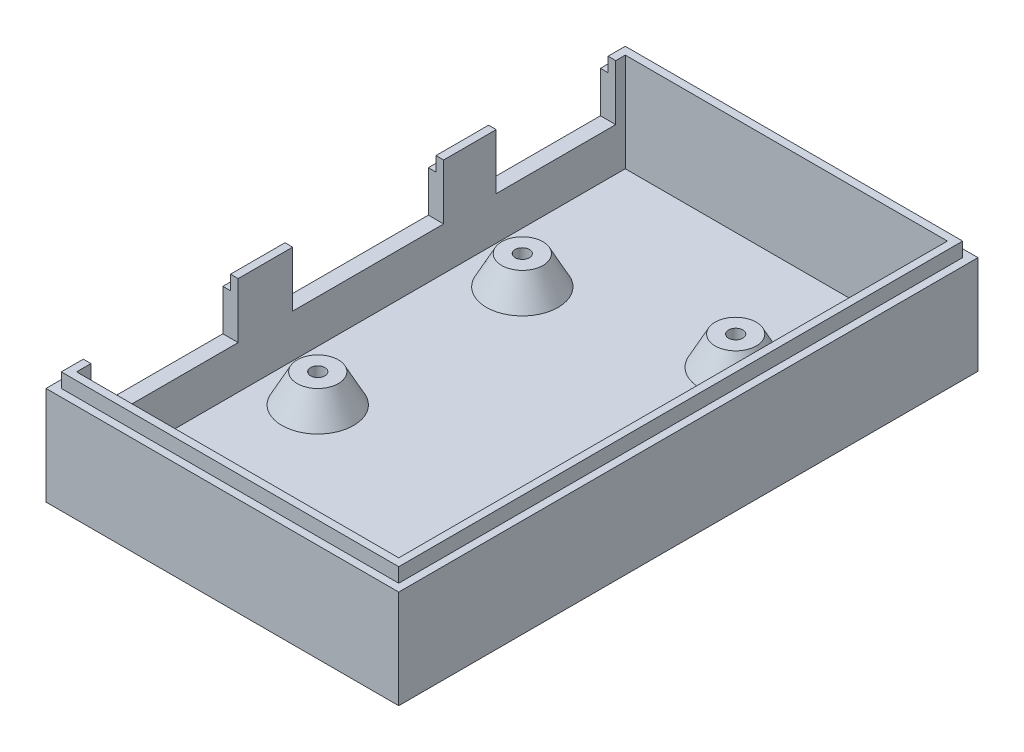
SolidWorks part; units mm, degrees
ref_plane "Спереди" through (0, 0, 0) normal (0, 0, 1) x (1, 0, 0)
ref_plane "Сверху" through (0, 0, 0) normal (0, 1, 0) x (1, 0, 0)
ref_plane "Справа" through (0, 0, 0) normal (1, 0, 0) x (0, 0, -1)
sketch "Эскиз1" plane through (0, 0, 0) normal (0, 1, 0) x (1, 0, 0)
  line L0 (347.1851, 1631.4336) -> (1749.4233, 1631.4336) construction
  line L2 (0, 0) -> (33.3, 0)
  line L3 (0, 0) -> (0, 57)
  line L4 (0, 57) -> (33.3, 57)
  line L5 (33.3, 0) -> (33.3, 57)
  circle A0 centre (5.1, 19.73) radius 0.75
  circle A1 centre (5.1, 41.13) radius 0.75
  circle A2 centre (23.55, 45) radius 0.75
  circle A3 centre (30.75, 12.6) radius 0.75
  dimension "D3" = 1.5
  dimension "D1" = 57
  dimension "D2" = 33.3
  dimension "D4" = 5.1
  dimension "D5" = 19.73
  dimension "D6" = 21.4
  dimension "D7" = 2.55
  dimension "D8" = 12.6
  dimension "D9" = 9.75
  dimension "D10" = 12
sketch "Эскиз2" plane through (0, 0, 0) normal (0, 1, 0) x (1, 0, 0)
  line L0 (0, 57) -> (33.3, 57) construction
  line L1 (33.3, 0) -> (33.3, 57) construction
  line L2 (0, 0) -> (33.3, 0) construction
  line L3 (0, 0) -> (0, 57) construction
  line L4 (0, 57) -> (33.3, 57) construction
  line L5 (33.3, 0) -> (33.3, 57) construction
  line L6 (0, 0) -> (33.3, 0) construction
  line L7 (0, 0) -> (0, 57) construction
  line L12 (-0.2, -0.2) -> (-0.2, 57.2)
  line L13 (-0.2, 57.2) -> (33.5, 57.2)
  line L14 (33.5, -0.2) -> (33.5, 57.2)
  line L15 (-0.2, -0.2) -> (33.5, -0.2)
  line L16 (-1.8, -1.8) -> (-1.8, 58.8)
  line L17 (-1.8, 58.8) -> (35.1, 58.8)
  line L18 (35.1, -1.8) -> (35.1, 58.8)
  line L19 (-1.8, -1.8) -> (35.1, -1.8)
  line L20 (-1, -1) -> (-1, 58) construction
  line L21 (-1, 58) -> (34.3, 58)
  line L22 (34.3, -1) -> (34.3, 58)
  line L23 (-1, -1) -> (34.3, -1)
  circle A0 centre (5.1, 19.73) radius 0.75 construction
  circle A1 centre (30.75, 12.6) radius 0.75 construction
  circle A2 centre (23.55, 45) radius 0.75 construction
  circle A3 centre (5.1, 41.13) radius 0.75 construction
  circle A4 centre (5.1, 19.73) radius 0.75
  circle A5 centre (30.75, 12.6) radius 0.75
  circle A6 centre (23.55, 45) radius 0.75
  circle A7 centre (5.1, 41.13) radius 0.75
  circle A8 centre (5.1, 41.13) radius 2.25
  circle A9 centre (23.55, 45) radius 2.25
  circle A10 centre (30.75, 12.6) radius 2.25
  circle A11 centre (5.1, 19.73) radius 2.25
  circle A12 centre (5.1, 41.13) radius 3.75
  circle A13 centre (23.55, 45) radius 3.75
  circle A14 centre (5.1, 19.73) radius 3.75
  arc A16 (33.5, 15.1495) -> (33.5, 10.0505) centre (30.75, 12.6) ccw
  point P30 (30.75, 12.6)
  point P32 (34.5, 12.6)
  dimension "D1" = 4.5
  dimension "D2" = 1.6
  dimension "D3" = 1.5
  dimension "D4" = 1.5
  dimension "D5" = 0.2
  dimension "D6" = 0.8
extrude "Бобышка-Вытянуть1" add sketch "Эскиз2" along normal blind 1.5 contours A5 | A10 A5 | L14 A16 A10 | A4 | A11 A4 | A14 A11 | A7 | A8 A7 | A12 A8 | A6 | A9 A6 | A13 A9 | A16 L14 L13 L12 L15 A14 A13 A12 | L16 L19 L18 L17 L15 L12 L13 L14 region at (16.737, 0, -28.3565) region at (27.0992, 0, -12.6) region at (-1.0905, 0, -28.5) region at (5.1, 0, -19.73) region at (30.75, 0, -12.6) region at (23.55, 0, -45) region at (5.1, 0, -41.13) region at (2.9136, 0, -41.13) region at (21.3636, 0, -45) region at (28.5636, 0, -12.6) region at (2.9136, 0, -19.73) region at (1.4561, 0, -41.13) region at (19.9061, 0, -45) region at (1.4561, 0, -19.73)
extrude "Бобышка-Вытянуть2" add sketch "Эскиз2<10>" along normal blind 3 draft 28 from surface contours A14 A11 | A11 A4 | L14 A16 A10 | A8 A7 | A12 A8 | A13 A9 | A7 | A9 A6 | A6 | A5 | A10 A5 | A4 region at (27.0992, 0, -12.6) region at (5.1, 0, -19.73) region at (30.75, 0, -12.6) region at (23.55, 0, -45) region at (5.1, 0, -41.13) region at (2.9136, 0, -41.13) region at (21.3636, 0, -45) region at (28.5636, 0, -12.6) region at (2.9136, 0, -19.73) region at (1.4561, 0, -41.13) region at (19.9061, 0, -45) region at (1.4561, 0, -19.73) starting at face at (16.65, 1.5, -28.5)
sketch "Эскиз2<10>" plane through (0, 0, 0) normal (0, 1, 0) x (1, 0, 0) same geometry as "Эскиз2"
extrude "Бобышка-Вытянуть3" add sketch "Эскиз2<11>" along normal offset from surface (4.5 mm away) 1.5 from surface contours L16 L19 L18 L17 L15 L12 L13 L14 region at (-1.0905, 0, -28.5) up to face at (5.1, 4.5, -17.5751) offset beyond the face yes starting at face at (5.1, 1.5, -15.98)
sketch "Эскиз2<11>" plane through (0, 0, 0) normal (0, 1, 0) x (1, 0, 0) same geometry as "Эскиз2"
sketch "Эскиз3" plane through (0, 6, 0) normal (0, 1, 0) x (1, 0, 0)
  line L0 (-1.8, 1.3) -> (-0.2, 1.3)
  line L1 (-1.8, 58.8) -> (-1.8, -1.8) construction
  line L2 (-0.2, -0.2) -> (-0.2, 57.2) construction
  line L3 (0, 0) -> (33.3, 0) construction
  line L4 (-1.8, 56.2) -> (-0.2, 56.2)
  line L5 (-0.2, 57.2) -> (-0.2, -0.2) construction
  line L6 (0, 57) -> (33.3, 57) construction
  line L7 (-1.8, 16.7) -> (-0.2, 16.7)
  line L8 (-1.8, 43.7) -> (-0.2, 43.7)
  line L9 (-1.8, 38.2) -> (-0.2, 38.2)
  line L10 (-1.8, -1.8) -> (-1.8, 58.8) construction
  line L11 (-1.8, 22.4) -> (-0.2, 22.4)
  line M7 (35.1, -1.8) -> (35.1, 58.8)
  line M8 (35.1, 58.8) -> (-1.8, 58.8)
  line M9 (-1.8, 58.8) -> (-1.8, -1.8)
  line M10 (-1.8, -1.8) -> (35.1, -1.8)
  line M11 (-0.2, 57.2) -> (33.5, 57.2)
  line M12 (33.5, 57.2) -> (33.5, -0.2)
  line M13 (33.5, -0.2) -> (-0.2, -0.2)
  line M14 (-0.2, -0.2) -> (-0.2, 57.2)
  dimension "D1" = 1.3
  dimension "D2" = 0.8
  dimension "D3" = 15.4
  dimension "D4" = 12.5
  dimension "D5" = 5.5
  dimension "D6" = 5.7
extrude "Бобышка-Вытянуть4" add sketch "Эскиз3" along normal blind 4.3 contours L4 L0 M9 M14 M11 M12 M13 M10 M7 M8 | L11 L7 M9 M14 | L9 L8 M9 M14 region at (-1, 6, -0.5905) region at (-1, 6, -19.55) region at (-1, 6, -40.95)
sketch "Эскиз5" plane through (0, 10.3, 0) normal (0, 1, 0) x (1, 0, 0)
  line L0 (-1, -1) -> (34.3, -1) construction
  line L1 (34.3, -1) -> (34.3, 58) construction
  line L2 (-1, 58) -> (34.3, 58) construction
  line L3 (-1, -1) -> (-1, 58) construction
  line L4 (-1, -1) -> (34.3, -1)
  line L5 (34.3, -1) -> (34.3, 58)
  line L6 (-1, 58) -> (34.3, 58)
  line L7 (-1, -1) -> (-1, 1.3)
  line L8 (-1.8, 43.7) -> (-0.2, 43.7) construction
  line L9 (-1.8, 38.2) -> (-0.2, 38.2) construction
  line L10 (-0.2, 38.2) -> (-0.2, 43.7) construction
  line L11 (-1, 43.7) -> (-0.2, 43.7)
  line L12 (-1, 38.2) -> (-0.2, 38.2)
  line L13 (-0.2, 38.2) -> (-0.2, 43.7)
  line L14 (-0.2, 16.7) -> (-0.2, 22.4) construction
  line L15 (-1.8, 16.7) -> (-0.2, 16.7) construction
  line L16 (-1.8, 22.4) -> (-0.2, 22.4) construction
  line L17 (-0.2, 16.7) -> (-0.2, 22.4)
  line L18 (-1, 16.7) -> (-0.2, 16.7)
  line L19 (-1, 22.4) -> (-0.2, 22.4)
  line L20 (-1, 38.2) -> (-1, 43.7)
  line L21 (-1.8, 56.2) -> (-0.2, 56.2) construction
  line L22 (-0.2, 56.2) -> (-0.2, 57.2) construction
  line L23 (-0.2, 57.2) -> (33.5, 57.2) construction
  line L24 (33.5, 57.2) -> (33.5, -0.2) construction
  line L25 (33.5, -0.2) -> (-0.2, -0.2) construction
  line L26 (-0.2, -0.2) -> (-0.2, 1.3) construction
  line L27 (-1.8, 1.3) -> (-0.2, 1.3) construction
  line L28 (-1, 56.2) -> (-0.2, 56.2)
  line L29 (-0.2, 56.2) -> (-0.2, 57.2)
  line L30 (-0.2, 57.2) -> (33.5, 57.2)
  line L31 (33.5, 57.2) -> (33.5, -0.2)
  line L32 (33.5, -0.2) -> (-0.2, -0.2)
  line L33 (-0.2, -0.2) -> (-0.2, 1.3)
  line L34 (-1, 1.3) -> (-0.2, 1.3)
  line L35 (-1, 16.7) -> (-1, 22.4)
  line L36 (-1, 56.2) -> (-1, 58)
extrude "Бобышка-Вытянуть5" add sketch "Эскиз5" along normal blind 1.5
extrude "Вырез-Вытянуть1" cut sketch "Эскиз2<12>" along normal up to surface (4.5 mm away) from surface contours A6 | A7 | A4 | A5 region at (5.1, 0, -19.73) region at (30.75, 0, -12.6) region at (23.55, 0, -45) region at (5.1, 0, -41.13) up to face at (23.55, 4.5, -42.8451) starting at face at (5.1, 1.5, -37.38)
sketch "Эскиз2<12>" plane through (0, 0, 0) normal (0, 1, 0) x (1, 0, 0) same geometry as "Эскиз2"
